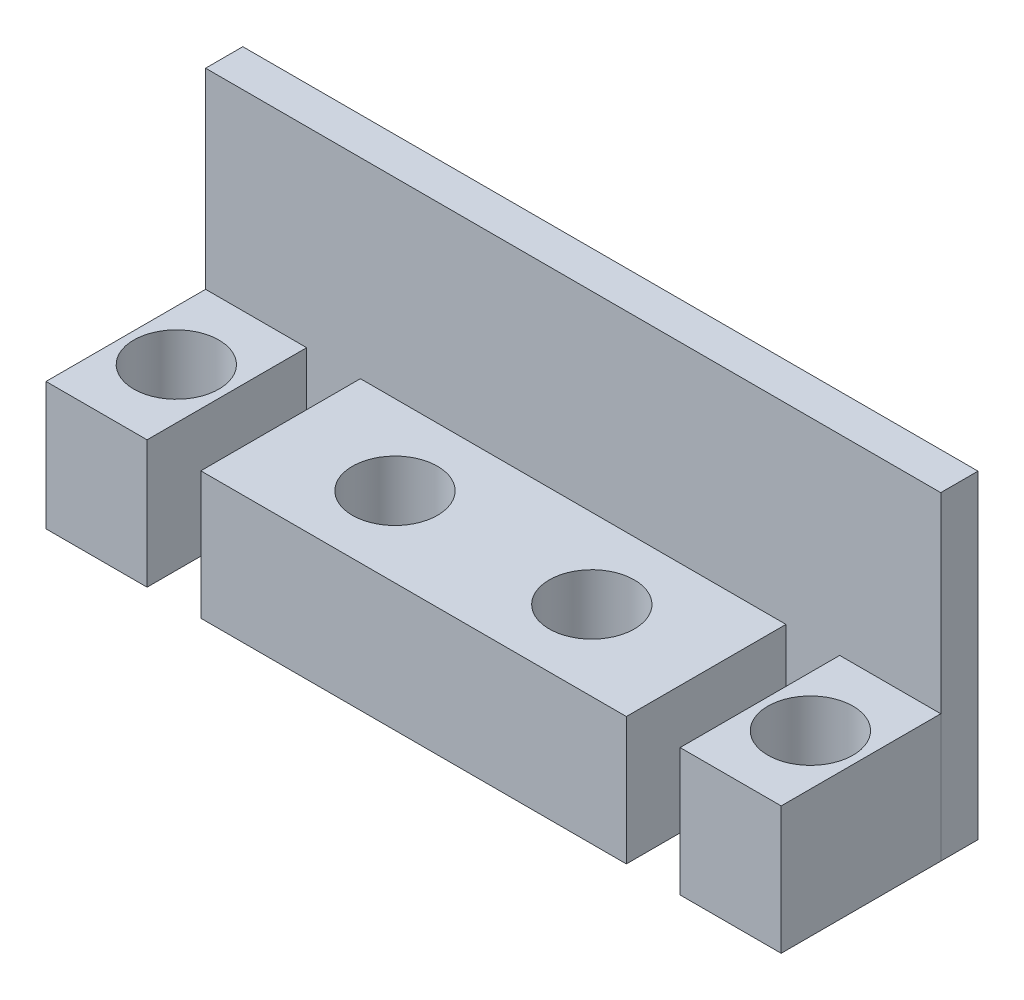
SolidWorks part; units mm, degrees
ref_plane "Front Plane" through (0, 0, 0) normal (0, 0, 1) x (1, 0, 0)
ref_plane "Top Plane" through (0, 0, 0) normal (0, 1, 0) x (1, 0, 0)
ref_plane "Right Plane" through (0, 0, 0) normal (1, 0, 0) x (0, 0, -1)
sketch "Sketch1" plane through (0, 0, 0) normal (0, 1, 0) x (1, 0, 0)
  line L0 (20, 15) -> (20, 0) construction
  line L1 (0, 0) -> (40, 0)
  line L2 (0, 0) -> (0, 15)
  line L3 (0, 15) -> (40, 15)
  line L4 (40, 0) -> (40, 15)
  line L5 (20, 7.5) -> (10.75, 7.5) construction
  line L6 (0, 7.5) -> (-5.05, 7.5) construction
  line L7 (54.55, 0) -> (45.05, 0)
  line L8 (-14.55, 15) -> (-5.05, 15)
  line L9 (-14.55, 15) -> (-14.55, 0)
  line L10 (-14.55, 0) -> (-5.05, 0)
  line L11 (-5.05, 15) -> (-5.05, 0)
  line L12 (45.05, 15) -> (45.05, 0)
  line L13 (54.55, 15) -> (45.05, 15)
  line L14 (54.55, 15) -> (54.55, 0)
  circle A0 centre (10.75, 7.5) radius 4
  circle A1 centre (29.25, 7.5) radius 4
  circle A2 centre (-9.8, 7.5) radius 4
  circle A3 centre (49.8, 7.5) radius 4
  dimension "D4" = 8
  dimension "D1" = 40
  dimension "D2" = 15
  dimension "D3" = 9.25
  dimension "D6" = 9.5
  dimension "D5" = 5.05
  dimension "D8" = 20.55
  dimension "D7" = 2
extrude "Boss-Extrude1" add sketch "Sketch1" along normal blind 12
ref_plane "Plane1" through (20, 0, 0) normal (-1, 0, 0) x (0, 0, 1)
sketch "Sketch2" plane through (20, 0, 0) normal (-1, 0, 0) x (0, 0, 1)
  line L1 (-15, 0) -> (-18.5, 0)
  line L2 (-15, 0) -> (-15, 30)
  line L3 (-15, 30) -> (-18.5, 30)
  line L4 (-18.5, 0) -> (-18.5, 30)
  dimension "D1" = 3.5
  dimension "D2" = 30
extrude "Boss-Extrude2" add sketch "Sketch2" along normal blind 34.55 and the other way blind 34.55
equation "\"verticalSlideWidth\"=9.5"
equation "\"D6@Sketch1\"=\"verticalSlideWidth\""
equation "\"D5@Sketch1\"=\"verticalSlideWidth\"*(-1)+14.55"
